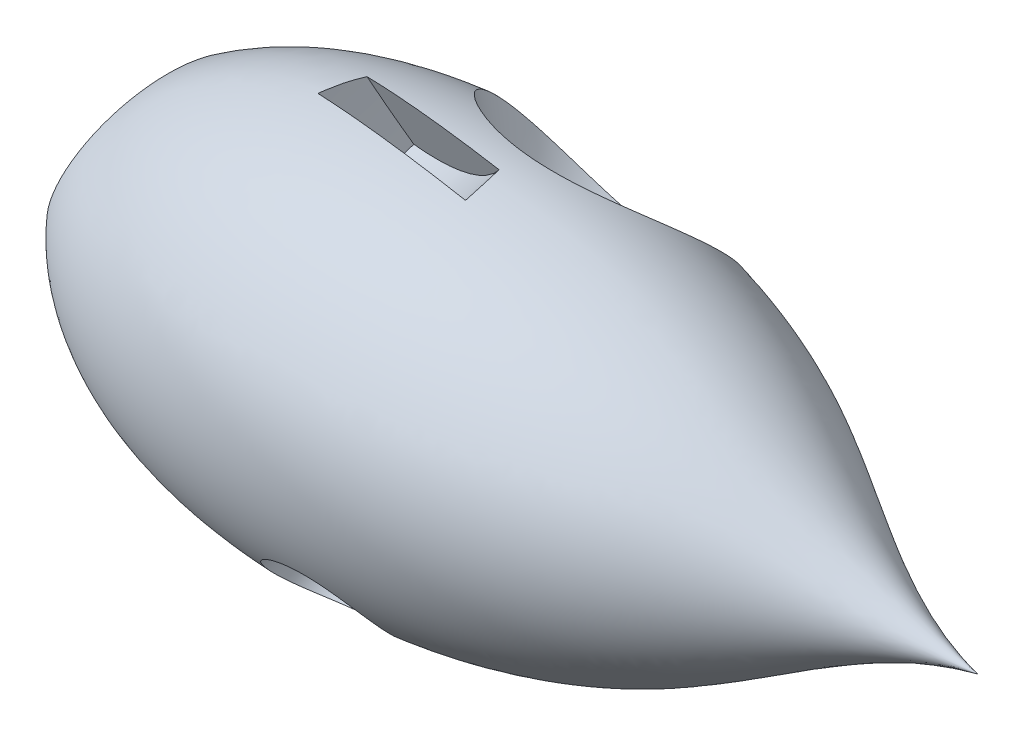
SolidWorks part; units mm, degrees
ref_plane "Piano frontale" through (0, 0, 0) normal (0, 0, 1) x (1, 0, 0)
ref_plane "Piano superiore" through (0, 0, 0) normal (0, 1, 0) x (1, 0, 0)
ref_plane "Piano destro" through (0, 0, 0) normal (1, 0, 0) x (0, 0, -1)
sketch "Schizzo1" plane through (0, 0, 0) normal (0, 0, 1) x (1, 0, 0)
  line L0 (-35.0064, 0) -> (50.7145, 0)
  spline S0 degree 3 poles (-35.0064, 0) (-29.3337, 14.1252) (-4.4532, 20.5112) (27.3364, 14.1041) (41.5267, 1.8396) (50.7145, 0) knots 0 0 0 0 0.432439 0.714134 1 1 1 1
revolve "Rivoluzione1" add sketch "Schizzo1" angle 360 about L0
sketch "Schizzo2" plane through (0.6224, 3.3855, -1.7527) normal (-0.1611, -0.8764, 0.4537) x (0.9869, -0.1431, 0.0741)
  line L0 (-12.9461, -18.3705) -> (5.2843, -17.5477)
  spline S2 degree 3 poles (6781.3763, 5822.0868) (-908.5817, -219.2317) (26.1288, -174.0376) (8.6156, -26.6644) (-20.2728, 62.1315) (-402.0425, -16.0972) (-1068.5496, -8925.276) knots -5.419249 -5.419249 -5.419249 -5.419249 0.383387 0.592138 0.788086 4.338639 4.338639 4.338639 4.338639 only from (-2.7579, -64.8512) to (-7.9283, -4.1977)
  spline S3 degree 3 poles (3288.3578, -8272.492) (944.0317, 333.395) (-673.0962, 68.6274) (437.8998, -345.7557) (6300.4602, 6320.1781) knots -9.167098 -9.167098 -9.167098 -9.167098 0.455078 7.083232 7.083232 7.083232 7.083232 only from (-7.9283, -4.1977) to (-2.7579, -64.8512)
  spline S4 degree 3 poles (-2.7579, -64.8512) (3.2759, -58.4871) (10.8391, -45.3749) (8.6156, -26.6644) (4.112, -12.8213) (-3.0672, -5.5887) (-7.9283, -4.1977) knots 0 0 0 0 0.383387 0.592138 0.788086 1 1 1 1
  spline S5 degree 3 poles (-7.9283, -4.1977) (-12.3017, -12.9371) (-17.1105, -34.424) (-11.5884, -56.4774) (-2.7579, -64.8512) knots 0 0 0 0 0.455078 1 1 1 1
  spline M3 degree 3 poles (-2.7579, -64.8512) (3.2759, -58.4871) (10.8391, -45.3749) (8.6156, -26.6644) (4.112, -12.8213) (-3.0672, -5.5887) (-7.9283, -4.1977) knots 0 0 0 0 0.383387 0.592138 0.788086 1 1 1 1
  spline M4 degree 3 poles (-7.9283, -4.1977) (-12.3017, -12.9371) (-17.1105, -34.424) (-11.5884, -56.4774) (-2.7579, -64.8512) knots 0 0 0 0 0.455078 1 1 1 1
  dimension "D1" = 0
extrude "Taglio-Estrusione1" cut sketch "Schizzo2" against normal blind 3.5 contours L0 M4 M3 region at (-3.9715, -1.8139, -13.4272)
sketch "Schizzo3" plane through (0.6275, 2.4408, -5.0257) normal (-0.1116, -0.4341, 0.8939) x (0.9938, -0.0488, 0.1004)
  line L0 (-12.7257, 18.9074) -> (6.4372, 20.6597)
  spline S2 degree 3 poles (158.8647, 6991.0862) (-343.7018, 59.5523) (-29.4988, -50.7114) (9.6118, 26.5478) (46.7779, 159.6161) (-741.2837, 331.0214) (4446.211, -5324.7794) knots -3.051354 -3.051354 -3.051354 -3.051354 0.211914 0.407862 0.616613 5.990574 5.990574 5.990574 5.990574 only from (-10.1841, 6.8863) to (4.2335, 66.0277)
  spline S3 degree 3 poles (4171.0478, -5528.7153) (408.6361, 259.8048) (-575.5132, 31.9789) (735.4468, -424.4871) (3684.0134, 5852.6938) knots -5.543544 -5.543544 -5.543544 -5.543544 0.544922 9.38708 9.38708 9.38708 9.38708 only from (4.2335, 66.0277) to (-10.1841, 6.8863)
  spline S4 degree 3 poles (-10.1841, 6.8863) (-5.1671, 7.5148) (3.037, 13.5599) (9.6118, 26.5478) (14.6805, 44.6955) (9.2192, 58.813) (4.2335, 66.0277) knots 0 0 0 0 0.211914 0.407862 0.616613 1 1 1 1
  spline S5 degree 3 poles (4.2335, 66.0277) (-5.7775, 59.1084) (-14.6187, 38.1637) (-13.1645, 16.1934) (-10.1841, 6.8863) knots 0 0 0 0 0.544922 1 1 1 1
  spline M3 degree 3 poles (-10.1841, 6.8863) (-5.1671, 7.5148) (3.037, 13.5599) (9.6118, 26.5478) (14.6805, 44.6955) (9.2192, 58.813) (4.2335, 66.0277) knots 0 0 0 0 0.211914 0.407862 0.616613 1 1 1 1
  spline M4 degree 3 poles (4.2335, 66.0277) (-5.7775, 59.1084) (-14.6187, 38.1637) (-13.1645, 16.1934) (-10.1841, 6.8863) knots 0 0 0 0 0.544922 1 1 1 1
  dimension "D1" = 0
extrude "Taglio-Estrusione2" cut sketch "Schizzo3" against normal blind 3.5 contours L0 M4 M3 region at (-3.9964, 15.9605, 0.963)
ref_plane "Piano1" through (0.0369, 0.4207, 0.5402) normal (0.0539, 0.6136, 0.7878) x (0.9985, -0.0331, -0.0425)
sketch "Schizzo4" plane through (0.0369, 0.4207, 0.5402) normal (0.0539, 0.6136, 0.7878) x (0.9985, -0.0331, -0.0425)
  line L4 (-26.233, 1.4477) -> (-26.2304, 1.4543)
  line L6 (-26.4869, 0.8849) -> (-14.2377, 1.5821)
  line L7 (-25.0927, 5.9605) -> (-25.0921, 5.9664)
  line L9 (-25.0006, 6.9664) -> (-14.2377, 1.5821)
  line L11 (-14.2377, 1.5821) -> (-54.67, 10.5993)
  circle A0 centre (-40.0296, 7.3342) radius 15 construction
  circle A1 centre (-40.0296, 7.3342) radius 15
  dimension "D3" = 1
revolve "Taglia-Rivoluzione2" cut sketch "Schizzo4" angle 360 about L11 rebuild error yes
revolve "Taglia-Rivoluzione3" cut sketch "Schizzo4<7>" angle 360 about L11 region at (-21.9255, 2.8653, 0.1385) region at (-41.3183, 2.6762, 1.6124)
sketch "Schizzo4<7>" plane through (0.0369, 0.4207, 0.5402) normal (0.0539, 0.6136, 0.7878) x (0.9985, -0.0331, -0.0425) same geometry as "Schizzo4"
scale "Scala1" scale about centroid uniform scaling yes scale factor 2
scale "Scala2" scale about centroid uniform scaling yes scale factor 0.7075
ref_plane "Piano2" through (1.6843, 9.0108, -10.4197) normal (0.1214, 0.6493, -0.7508) x (-0.9926, 0.0794, -0.0918)
hole_wizard "Foro svasato per Vite M6-3" positions "Schizzo3D9" profile "Schizzo13" countersink size "M6" standard "Ansi Metric" end condition through all
sketch3d "Schizzo3D9"
  point P0 (4.7832, 17.4233, -18.1102)
sketch "Schizzo13" plane through (4.7832, 17.4233, -18.1102) normal (0.5673, 0.5673, 0.5969) x (-0.8209, 0.4468, 0.3557)
  line L0 (0, 0) -> (0, 68.6589)
  line L1 (0, 68.6589) -> (7, 68.6589)
  line L2 (7, 68.6589) -> (7, 10.5)
  line L3 (7, 10.5) -> (17.5, 0)
  line L5 (17.5, 0) -> (0, 0)
  line L6 (-7, 10.5) -> (-17.5, 0) construction
  line L11 (0, -6.35) -> (0, 107.95) construction
  dimension "Thru Hole Dia." = 14
  dimension "Thru Hole Depth" = 68.6589
  dimension "Near C'Sink Dia." = 35
  dimension "Near C'Sink Angle" = 90
ref_plane "Piano3" through (-3.1702, -16.9605, 19.6124) normal (0.1214, 0.6493, -0.7508) x (-0.9926, 0.0794, -0.0918)
sketch "Schizzo14" plane through (-3.1702, -16.9605, 19.6124) normal (0.1214, 0.6493, -0.7508) x (-0.9926, 0.0794, -0.0918)
  line L0 (-4.5361, 5.7177) -> (-4.5361, -8.2619)
  line L1 (-11.4834, -1.2721) -> (2.4151, -1.2721)
  circle A0 centre (-4.5361, -1.2721) radius 7.5
  spline S0 degree 3 poles (-4.0768, 5.7169) (-4.9954, 5.7186) (-5.4481, 5.6735) (-6.1176, 5.5393) (-6.3391, 5.4833) (-6.7788, 5.3484) (-6.9971, 5.2692) (-7.632, 5.0024) (-8.0339, 4.7843) (-8.6048, 4.3973) (-8.7906, 4.2574) (-9.1457, 3.9612) (-9.3147, 3.8053) (-9.7969, 3.3149) (-10.0855, 2.9579) (-10.5942, 2.1817) (-10.8071, 1.7731) (-11.0639, 1.1356) (-11.1391, 0.9187) (-11.2685, 0.476) (-11.3227, 0.2491) (-11.4498, -0.4309) (-11.4889, -0.8871) (-11.4768, -1.805) (-11.4242, -2.27) (-11.231, -3.166) (-11.0912, -3.6018) (-10.8151, -4.2369) (-10.7119, -4.4454) (-10.4877, -4.8468) (-10.3662, -5.0411) (-10.105, -5.4168) (-9.9652, -5.5984) (-9.6669, -5.9486) (-9.5076, -6.1181) (-9.0079, -6.5998) (-8.6481, -6.8841) (-7.8765, -7.3812) (-7.4599, -7.5955) (-6.6059, -7.9341) (-6.1669, -8.0606) (-5.4904, -8.1863) (-5.2607, -8.2174) (-4.8045, -8.2566) (-4.5773, -8.2649) (-3.8983, -8.2569) (-3.4477, -8.2077) (-2.5588, -8.0206) (-2.1323, -7.8854) (-1.5177, -7.6228) (-1.317, -7.5252) (-0.9242, -7.3094) (-0.7325, -7.1912) (-0.1817, -6.8132) (0.1572, -6.5278) (0.6238, -6.0489) (0.773, -5.8798) (1.0533, -5.5282) (1.184, -5.3465) (1.5482, -4.7838) (1.7543, -4.3853) (2.0064, -3.7507) (2.0805, -3.5332) (2.2061, -3.0957) (2.3099, -2.6534) (2.3707, -2.2015) (2.4097, -1.7446) (2.4181, -1.5123) (2.4094, -0.8186) (2.359, -0.3626) (2.1717, 0.5367) (2.0325, 0.9837) (1.6775, 1.8282) (1.4617, 2.2298) (1.0798, 2.8013) (0.9427, 2.9863) (0.6547, 3.3383) (0.5032, 3.5064) (0.1853, 3.8267) (0.0189, 3.9791) (-0.3292, 4.2681) (-0.5119, 4.4054) (-1.0752, 4.787) (-1.47, 5.0014) (-2.2984, 5.3518) (-2.7366, 5.4884) (-3.6252, 5.6701) (-4.0768, 5.7169) (-4.9954, 5.7186) (-5.4481, 5.6735) knots -0.03125 -0.03125 0 0 0.03125 0.03125 0.046875 0.046875 0.0625 0.0625 0.09375 0.09375 0.109375 0.109375 0.125 0.125 0.15625 0.15625 0.1875 0.1875 0.203125 0.203125 0.21875 0.21875 0.25 0.25 0.28125 0.28125 0.3125 0.3125 0.328125 0.328125 0.34375 0.34375 0.359375 0.359375 0.375 0.375 0.40625 0.40625 0.4375 0.4375 0.46875 0.46875 0.484375 0.484375 0.5 0.5 0.53125 0.53125 0.5625 0.5625 0.578125 0.578125 0.59375 0.59375 0.625 0.625 0.640625 0.640625 0.65625 0.65625 0.6875 0.6875 0.703125 0.703125 0.71875 0.734375 0.734375 0.75 0.75 0.78125 0.78125 0.8125 0.8125 0.84375 0.84375 0.859375 0.859375 0.875 0.875 0.890625 0.890625 0.90625 0.90625 0.9375 0.9375 0.96875 0.96875 1 1 1.03125 1.03125 1.046875 only from (-4.5361, 5.7177) to (-4.5361, 5.7177) construction
  spline S1 degree 3 poles (-4.0768, 5.7169) (-4.9954, 5.7186) (-5.4481, 5.6735) (-6.1176, 5.5393) (-6.3391, 5.4833) (-6.7788, 5.3484) (-6.9971, 5.2692) (-7.632, 5.0024) (-8.0339, 4.7843) (-8.6048, 4.3973) (-8.7906, 4.2574) (-9.1457, 3.9612) (-9.3147, 3.8053) (-9.7969, 3.3149) (-10.0855, 2.9579) (-10.5942, 2.1817) (-10.8071, 1.7731) (-11.0639, 1.1356) (-11.1391, 0.9187) (-11.2685, 0.476) (-11.3227, 0.2491) (-11.4498, -0.4309) (-11.4889, -0.8871) (-11.4768, -1.805) (-11.4242, -2.27) (-11.231, -3.166) (-11.0912, -3.6018) (-10.8151, -4.2369) (-10.7119, -4.4454) (-10.4877, -4.8468) (-10.3662, -5.0411) (-10.105, -5.4168) (-9.9652, -5.5984) (-9.6669, -5.9486) (-9.5076, -6.1181) (-9.0079, -6.5998) (-8.6481, -6.8841) (-7.8765, -7.3812) (-7.4599, -7.5955) (-6.6059, -7.9341) (-6.1669, -8.0606) (-5.4904, -8.1863) (-5.2607, -8.2174) (-4.8045, -8.2566) (-4.5773, -8.2649) (-3.8983, -8.2569) (-3.4477, -8.2077) (-2.5588, -8.0206) (-2.1323, -7.8854) (-1.5177, -7.6228) (-1.317, -7.5252) (-0.9242, -7.3094) (-0.7325, -7.1912) (-0.1817, -6.8132) (0.1572, -6.5278) (0.6238, -6.0489) (0.773, -5.8798) (1.0533, -5.5282) (1.184, -5.3465) (1.5482, -4.7838) (1.7543, -4.3853) (2.0064, -3.7507) (2.0805, -3.5332) (2.2061, -3.0957) (2.3099, -2.6534) (2.3707, -2.2015) (2.4097, -1.7446) (2.4181, -1.5123) (2.4094, -0.8186) (2.359, -0.3626) (2.1717, 0.5367) (2.0325, 0.9837) (1.6775, 1.8282) (1.4617, 2.2298) (1.0798, 2.8013) (0.9427, 2.9863) (0.6547, 3.3383) (0.5032, 3.5064) (0.1853, 3.8267) (0.0189, 3.9791) (-0.3292, 4.2681) (-0.5119, 4.4054) (-1.0752, 4.787) (-1.47, 5.0014) (-2.2984, 5.3518) (-2.7366, 5.4884) (-3.6252, 5.6701) (-4.0768, 5.7169) (-4.9954, 5.7186) (-5.4481, 5.6735) knots -0.03125 -0.03125 0 0 0.03125 0.03125 0.046875 0.046875 0.0625 0.0625 0.09375 0.09375 0.109375 0.109375 0.125 0.125 0.15625 0.15625 0.1875 0.1875 0.203125 0.203125 0.21875 0.21875 0.25 0.25 0.28125 0.28125 0.3125 0.3125 0.328125 0.328125 0.34375 0.34375 0.359375 0.359375 0.375 0.375 0.40625 0.40625 0.4375 0.4375 0.46875 0.46875 0.484375 0.484375 0.5 0.5 0.53125 0.53125 0.5625 0.5625 0.578125 0.578125 0.59375 0.59375 0.625 0.625 0.640625 0.640625 0.65625 0.65625 0.6875 0.6875 0.703125 0.703125 0.71875 0.734375 0.734375 0.75 0.75 0.78125 0.78125 0.8125 0.8125 0.84375 0.84375 0.859375 0.859375 0.875 0.875 0.890625 0.890625 0.90625 0.90625 0.9375 0.9375 0.96875 0.96875 1 1 1.03125 1.03125 1.046875 only from (-4.5361, 5.7177) to (-4.5361, 5.7177)
  dimension "D1" = 15
extrude "Taglio-Estrusione3" cut sketch "Schizzo14" along normal blind 7 contours A0 S1 | L1 S1 L0 | L0 S1 L1 | L1 S1 L0 | L0 S1 L1 region at (-1.5848, -15.8099, 20.8637) region at (4.2594, -16.273, 21.4078) region at (-1.6135, -20.3048, 16.9719) region at (4.2529, -20.7512, 17.5341) region at (8.5664, -18.8614, 19.8657)
scale "Scala7" scale about centroid uniform scaling yes scale factor 1.5
